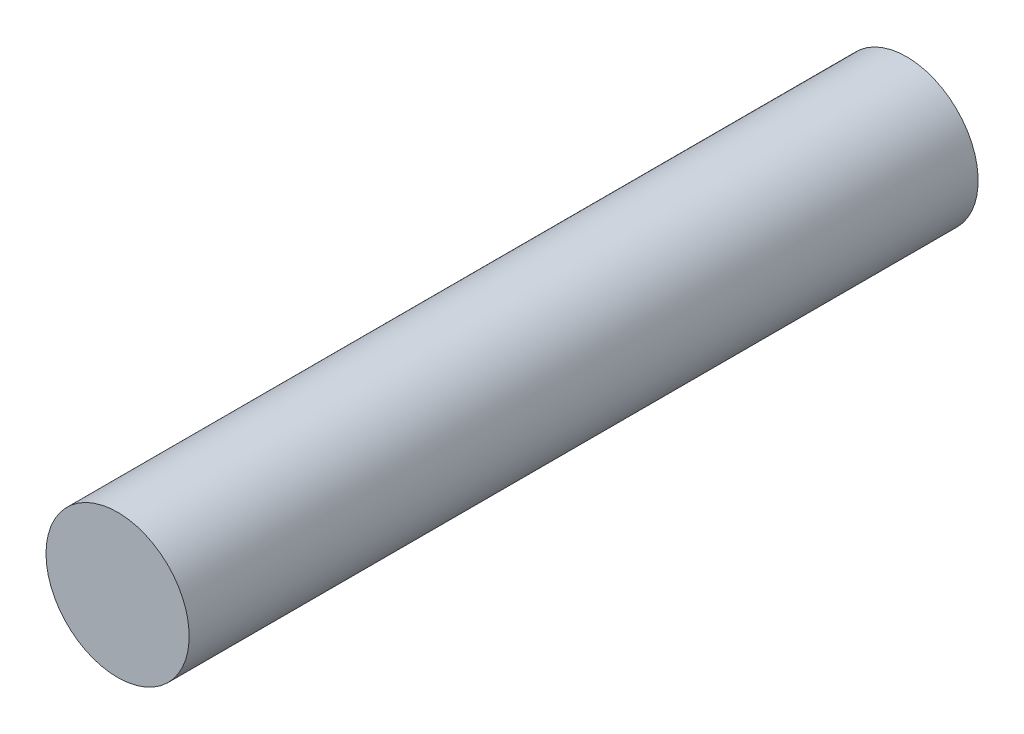
SolidWorks part; units mm, degrees
ref_plane "Front Plane" through (0, 0, 0) normal (0, 0, 1) x (1, 0, 0)
ref_plane "Top Plane" through (0, 0, 0) normal (0, 1, 0) x (1, 0, 0)
ref_plane "Right Plane" through (0, 0, 0) normal (1, 0, 0) x (0, 0, -1)
sketch "Sketch1" plane through (0, 0, 0) normal (0, 0, 1) x (1, 0, 0)
  circle A0 centre (0, 0) radius 4.5
  dimension "D1" = 9
extrude "Boss-Extrude1" add sketch "Sketch1" along normal blind 49.6
